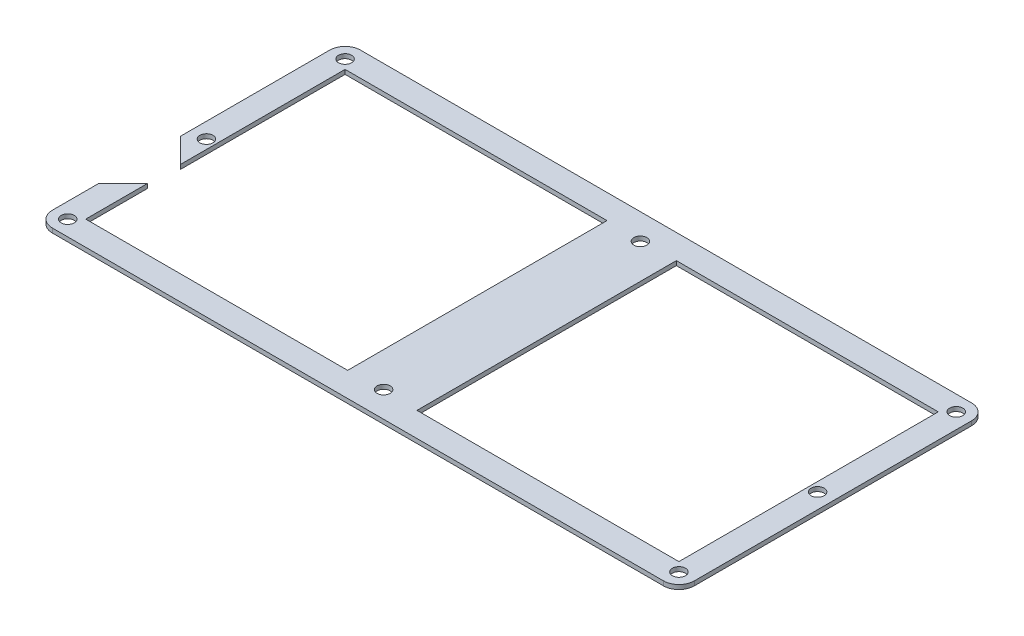
SolidWorks part; units mm, degrees
ref_plane "前视基准面" through (0, 0, 0) normal (0, 0, 1) x (1, 0, 0)
ref_plane "上视基准面" through (0, 0, 0) normal (0, 1, 0) x (1, 0, 0)
ref_plane "右视基准面" through (0, 0, 0) normal (1, 0, 0) x (0, 0, -1)
sketch "草图3" plane through (0, 0, 0) normal (0, 1, 0) x (1, 0, 0)
  line L16 (9.3459, 60.0215) -> (9.3459, 118.0215)
  line L17 (15.3459, 124.0215) -> (253.3459, 124.0215)
  line L18 (259.3459, 118.0215) -> (259.3459, 10.0215)
  line L19 (253.3459, 4.0215) -> (15.3459, 4.0215)
  line L20 (9.3459, 10.0215) -> (9.3459, 28.0215)
  line L21 (18.8459, 50.5215) -> (9.3459, 60.0215)
  line L22 (18.8459, 37.5215) -> (9.3459, 28.0215)
  line L23 (148.8459, 114.5215) -> (249.8459, 114.5215)
  line L24 (249.8459, 114.5215) -> (249.8459, 13.5215)
  line L25 (249.8459, 13.5215) -> (148.8459, 13.5215)
  line L26 (18.8459, 37.5215) -> (18.8459, 13.5215)
  line L27 (18.8459, 13.5215) -> (119.8459, 13.5215)
  line L28 (119.8459, 114.5215) -> (18.8459, 114.5215)
  line L29 (18.8459, 114.5215) -> (18.8459, 50.5215)
  line L30 (119.8459, 114.5215) -> (120.8459, 114.5215)
  line L31 (120.8459, 114.5215) -> (120.8459, 13.5215)
  line L32 (120.8459, 13.5215) -> (119.8459, 13.5215)
  line L33 (148.8459, 114.5215) -> (147.8459, 114.5215)
  line L34 (147.8459, 114.5215) -> (147.8459, 13.5215)
  line L35 (147.8459, 13.5215) -> (148.8459, 13.5215)
  arc A12 (15.3459, 124.0215) -> (9.3459, 118.0215) centre (15.3459, 118.0215) ccw
  arc A13 (259.3459, 118.0215) -> (253.3459, 124.0215) centre (253.3459, 118.0215) ccw
  arc A14 (253.3459, 4.0215) -> (259.3459, 10.0215) centre (253.3459, 10.0215) ccw
  arc A15 (9.3459, 10.0215) -> (15.3459, 4.0215) centre (15.3459, 10.0215) ccw
  circle A16 centre (15.3459, 118.0215) radius 2.55
  circle A17 centre (253.3459, 118.0215) radius 2.55
  circle A18 centre (134.3459, 114.0215) radius 2.55
  circle A19 centre (15.3459, 10.0215) radius 2.55
  circle A20 centre (253.3459, 10.0215) radius 2.55
  circle A21 centre (134.3459, 14.0215) radius 2.55
  circle A22 centre (253.3459, 64.0215) radius 2.55
  circle A23 centre (15.3459, 64.0215) radius 2.55
  point P39 (0, 0.001)
  point P40 (0.001, 0.001)
  point P41 (0.001, 0)
  dimension "D1" = 101
  dimension "D2" = 101
  dimension "D3" = 102
extrude "凸台-拉伸1" add sketch "草图3" along normal blind 1.7
